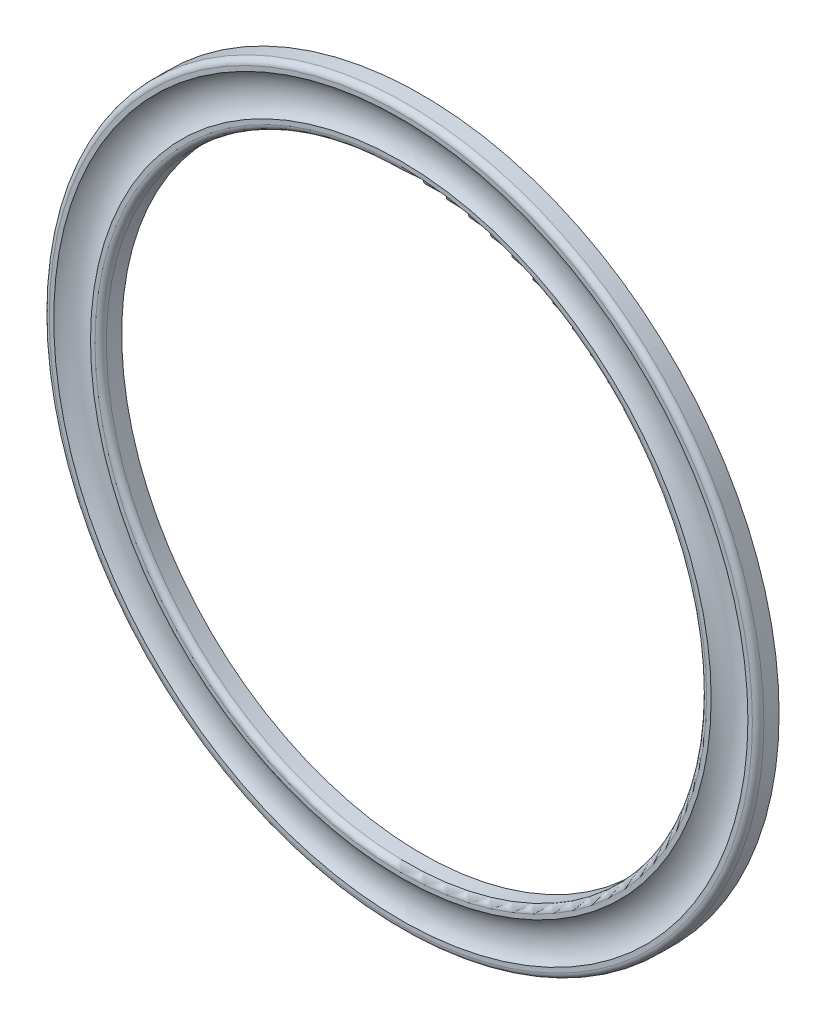
SolidWorks part; units mm, degrees
ref_plane "前基準面" through (0, 0, 0) normal (0, 0, 1) x (1, 0, 0)
ref_plane "上基準面" through (0, 0, 0) normal (0, 1, 0) x (1, 0, 0)
ref_plane "右基準面" through (0, 0, 0) normal (1, 0, 0) x (0, 0, -1)
ref_axis "基準軸1" through (0, -55, 0) along (0, 1, 0)
ref_axis "基準軸2" through (-88.99, 0, 0) along (1, 0, 0)
ref_axis "基準軸3" through (0, 0, 55) along (0, 0, -1)
sketch "草圖3" plane through (0, 0, 0) normal (0, 1, 0) x (1, 0, 0)
  line L1 (-10, 15) -> (10, 15)
  line L2 (0, -55) -> (0, 55) construction
  line L3 (-10, 15) -> (-10, 9.6604)
  line L4 (-8, 7.6604) -> (-6.4279, 7.6604)
  line L5 (10, 15) -> (10, 9.6604)
  line L6 (8, 7.6604) -> (6.4279, 7.6604)
  line L7 (-11, 0) -> (11, 0) construction
  arc A0 (6.4279, 7.6604) -> (-6.4279, 7.6604) centre (0, 0) ccw
  arc A1 (-10, 9.6604) -> (-8, 7.6604) centre (-8, 9.6604) ccw
  arc A2 (10, 9.6604) -> (8, 7.6604) centre (8, 9.6604) cw
  point P8 (0, 15)
  dimension "D2" = 10
  dimension "D5" = 2
  dimension "D6" = 2
  dimension "D1" = 80
  dimension "D3" = 20
  dimension "D4" = 15
ref_plane "平面1" through (115, 0, 0) normal (1, 0, 0) x (0, 0, -1)
ref_axis "基準軸7" through (115, 0, 57.074) along (0, 0, -1)
revolve "旋轉2" add sketch "草圖3" angle 360 about axis through (115, 0, 57.074) along (0, 0, -1)
